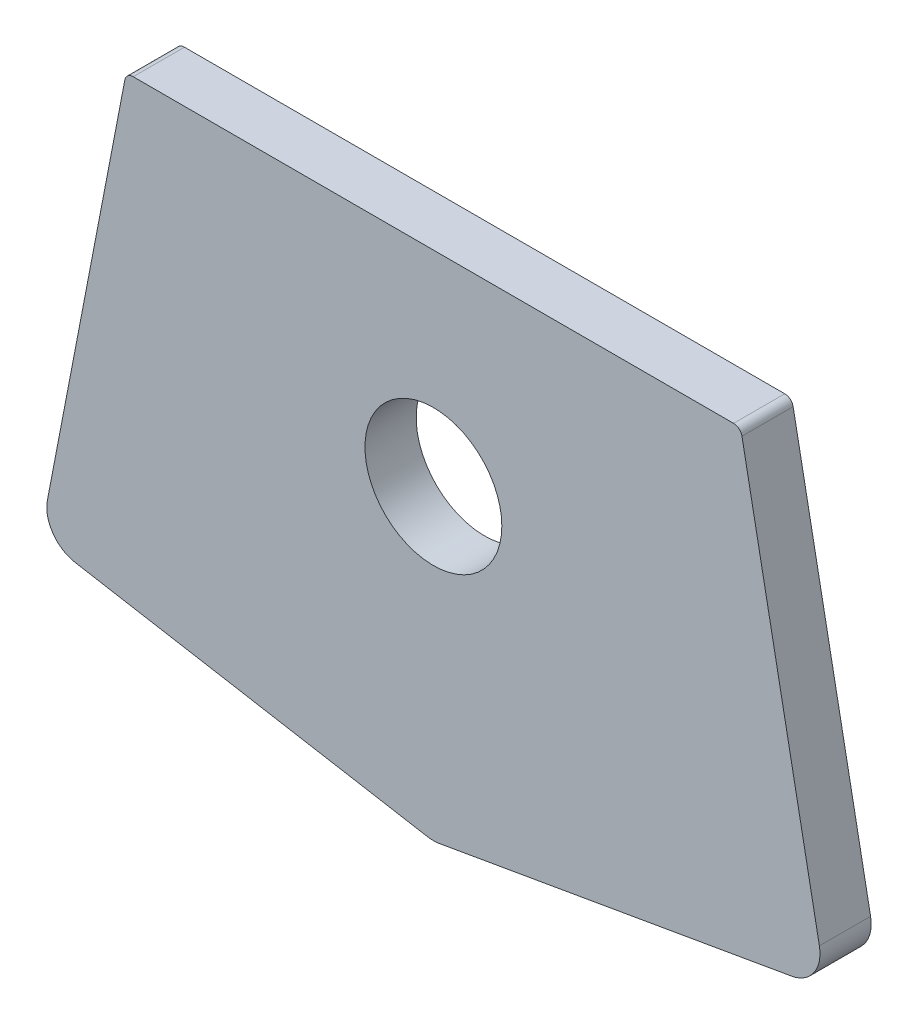
SolidWorks part; units mm, degrees
ref_plane "前视基准面" through (0, 0, 0) normal (0, 0, 1) x (1, 0, 0)
ref_plane "上视基准面" through (0, 0, 0) normal (0, 1, 0) x (1, 0, 0)
ref_plane "右视基准面" through (0, 0, 0) normal (1, 0, 0) x (0, 0, -1)
sketch "草图1" plane through (0, 0, 0) normal (0, 0, 1) x (1, 0, 0)
  line L0 (0, 6.5533) -> (0, -4.5416) construction
  line L1 (0, -30) -> (-23, -26)
  line L2 (-23, -26) -> (-18, 0)
  line L16 (23, -26) -> (18, 0)
  line L17 (0, -30) -> (23, -26)
  line L19 (-18, 0) -> (18, 0)
  circle A0 centre (0, -12) radius 4.01
  dimension "D3" = 12
  dimension "D4" = 8.02
  dimension "D1" = 36
  dimension "D2" = 30
  dimension "D7" = 46
  dimension "D8" = 4
extrude "凸台-拉伸1" add sketch "草图1" along normal mid plane 3
fillet "圆角1" radius 2 3 edges at (23, -26, 0) (0, -30, 0) (-23, -26, 0)
fillet "圆角2" radius 0.5 2 edges at (18, 0, 0) (-18, 0, 0)
